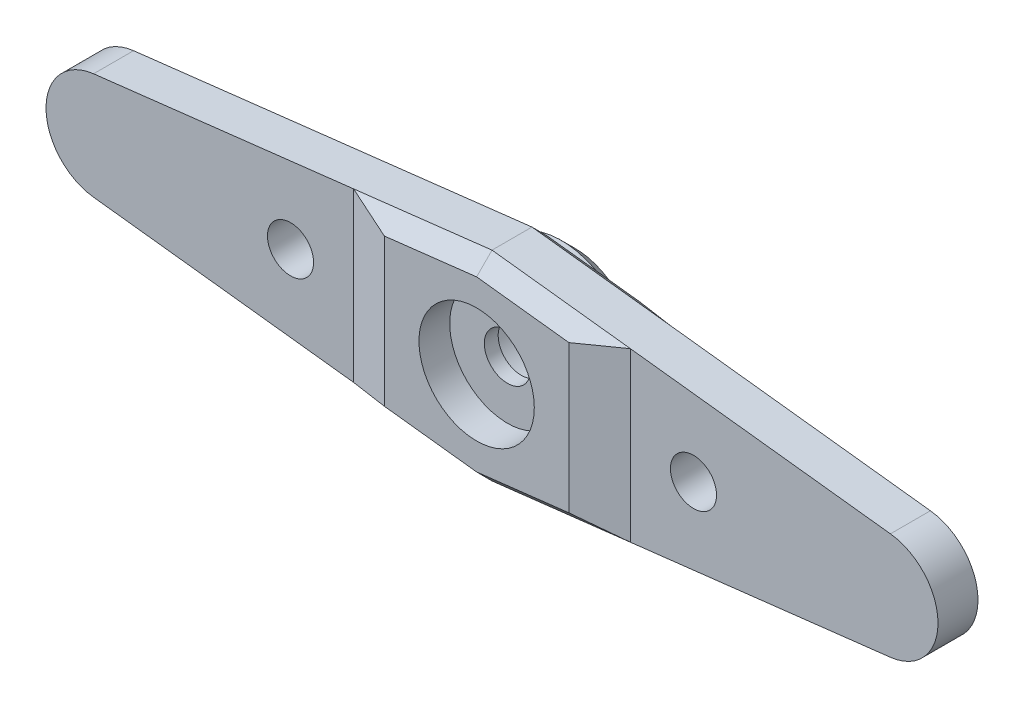
SolidWorks part; units mm, degrees
ref_plane "正面" through (0, 0, 0) normal (0, 0, 1) x (1, 0, 0)
ref_plane "平面" through (0, 0, 0) normal (0, 1, 0) x (1, 0, 0)
ref_plane "右側面" through (0, 0, 0) normal (1, 0, 0) x (0, 0, -1)
sketch "ｽｹｯﾁ1" plane through (0, 0, 0) normal (0, 0, 1) x (1, 0, 0)
  line L0 (0, 6.5) -> (25.9057, 3.4764)
  line L2 (25.9057, -3.4764) -> (0, -6.5)
  line L3 (0, -6.5) -> (-25.9057, -3.4764)
  line L5 (-25.9057, 3.4764) -> (0, 6.5)
  line L6 (0, 6.5) -> (0, 0) construction
  line L7 (0, 0) -> (0, -6.5) construction
  line L8 (25.5, 0) -> (-25.5, 0) construction
  arc A0 (25.9057, 3.4764) -> (25.9057, -3.4764) centre (25.5, 0) cw
  arc A1 (-25.9057, -3.4764) -> (-25.9057, 3.4764) centre (-25.5, 0) cw
  dimension "D9" = 3.5
  dimension "D10" = 3.5
  dimension "D1" = 6.5
  dimension "D2" = 6.5
  dimension "D3" = 25.5
  dimension "D4" = 25.5
extrude "ﾎﾞｽ - 押し出し1" add sketch "ｽｹｯﾁ1" along normal blind 2.6
sketch "ｽｹｯﾁ8" plane through (0, 0, 2.6) normal (0, 0, 1) x (1, 0, 0)
  line L0 (0, 6.5) -> (0, -6.5) construction
  line L1 (0, 0) -> (29, 0) construction
  line L2 (0, 0) -> (-29, 0) construction
  arc A0 (25.9057, -3.4764) -> (25.9057, 3.4764) centre (25.5, 0) ccw construction
  arc A1 (-25.9057, 3.4764) -> (-25.9057, -3.4764) centre (-25.5, 0) ccw construction
  circle A2 centre (13.1, 0) radius 1.5
  circle A3 centre (-13.1, 0) radius 1.5
  dimension "D3" = 3
  dimension "D4" = 3
  dimension "D1" = 13.1
  dimension "D2" = 13.1
extrude "ｶｯﾄ - 押し出し4" cut sketch "ｽｹｯﾁ8" against normal through all
sketch "ｽｹｯﾁ2" plane through (0, 0, 2.6) normal (0, 0, 1) x (1, 0, 0)
  line L0 (-9, 5.4496) -> (-9, -5.4496)
  line L1 (0, 6.5) -> (-25.9057, 3.4764) construction
  line L2 (-25.9057, -3.4764) -> (0, -6.5) construction
  line L3 (-9, -5.4496) -> (0, -6.5)
  line L4 (0, -6.5) -> (9, -5.4496)
  line L5 (0, -6.5) -> (25.9057, -3.4764) construction
  line L6 (9, -5.4496) -> (9, 5.4496)
  line L7 (25.9057, 3.4764) -> (0, 6.5) construction
  line L8 (9, 5.4496) -> (0, 6.5)
  line L9 (0, 6.5) -> (-9, 5.4496)
  dimension "D1" = 9
  dimension "D2" = 9
extrude "ﾎﾞｽ - 押し出し2" add sketch "ｽｹｯﾁ2" along normal blind 1
chamfer "面取り1" distance 1 angle 45 4 edges at (4.5, -5.9748, 3.6) (-4.5, -5.9748, 3.6) (-4.5, 5.9748, 3.6) (4.5, 5.9748, 3.6)
chamfer "面取り2" distance 1 distance2 3 2 edges at (9, 0, 3.6) (-9, 0, 3.6) first distance on face at (9, 0, 3.1) first distance on face at (-9, 0, 3.1)
sketch "ｽｹｯﾁ5" plane through (0, 0, 0) normal (0, 0, -1) x (-1, 0, 0)
  line L0 (9, 5.4496) -> (9, -5.4496)
  line L1 (0, 6.5) -> (25.9057, 3.4764) construction
  line L2 (25.9057, -3.4764) -> (0, -6.5) construction
  line L3 (9, -5.4496) -> (0, -6.5)
  line L4 (0, -6.5) -> (-9, -5.4496)
  line L5 (0, -6.5) -> (-25.9057, -3.4764) construction
  line L6 (-9, -5.4496) -> (-9, 5.4496)
  line L7 (-25.9057, 3.4764) -> (0, 6.5) construction
  line L8 (-9, 5.4496) -> (0, 6.5)
  line L9 (0, 6.5) -> (9, 5.4496)
  dimension "D1" = 9
  dimension "D2" = 9
extrude "ﾎﾞｽ - 押し出し3" add sketch "ｽｹｯﾁ5" along normal blind 1
sketch "ｽｹｯﾁ3" plane through (0, 0, 3.6) normal (0, 0, 1) x (1, 0, 0)
  line L0 (0, -5.4932) -> (0, 5.4932) construction
  line L2 (6, -4.7929) -> (6, 4.7929) construction
  line L3 (6, 0) -> (-6, 0) construction
  line L4 (-6, 4.7929) -> (-6, -4.7929) construction
  circle A0 centre (0, 0) radius 1.5
  dimension "D1" = 3
extrude "ｶｯﾄ - 押し出し1" cut sketch "ｽｹｯﾁ3" against normal through all
sketch "ｽｹｯﾁ4" plane through (0, 0, 3.6) normal (0, 0, 1) x (1, 0, 0)
  circle A0 centre (0, 0) radius 3.75
  dimension "D1" = 7.5
extrude "ｶｯﾄ - 押し出し2" cut sketch "ｽｹｯﾁ4" against normal blind 2
chamfer "面取り3" distance 1 angle 45 4 edges at (-4.5, 5.9748, -1) (4.5, 5.9748, -1) (4.5, -5.9748, -1) (-4.5, -5.9748, -1)
chamfer "面取り4" distance 1 distance2 3 2 edges at (9, 0, -1) (-9, 0, -1) first distance on face at (9, 0, -0.5) first distance on face at (-9, 0, -0.5)
sketch "ｽｹｯﾁ6" plane through (0, 0, -1) normal (0, 0, -1) x (-1, 0, 0)
  circle A0 centre (0, 0) radius 4.8
  dimension "D1" = 9.6
extrude "ﾎﾞｽ - 押し出し4" add sketch "ｽｹｯﾁ6" along normal blind 1.8
chamfer "面取り5" distance 0.9 angle 45 1 edges at (-4.8, 0, -2.8)
sketch "ｽｹｯﾁ7" plane through (0, 0, -2.8) normal (0, 0, -1) x (-1, 0, 0)
  circle A0 centre (0, 0) radius 2.9
  dimension "D1" = 5.8
extrude "ｶｯﾄ - 押し出し3" cut sketch "ｽｹｯﾁ7" against normal blind 3.5
